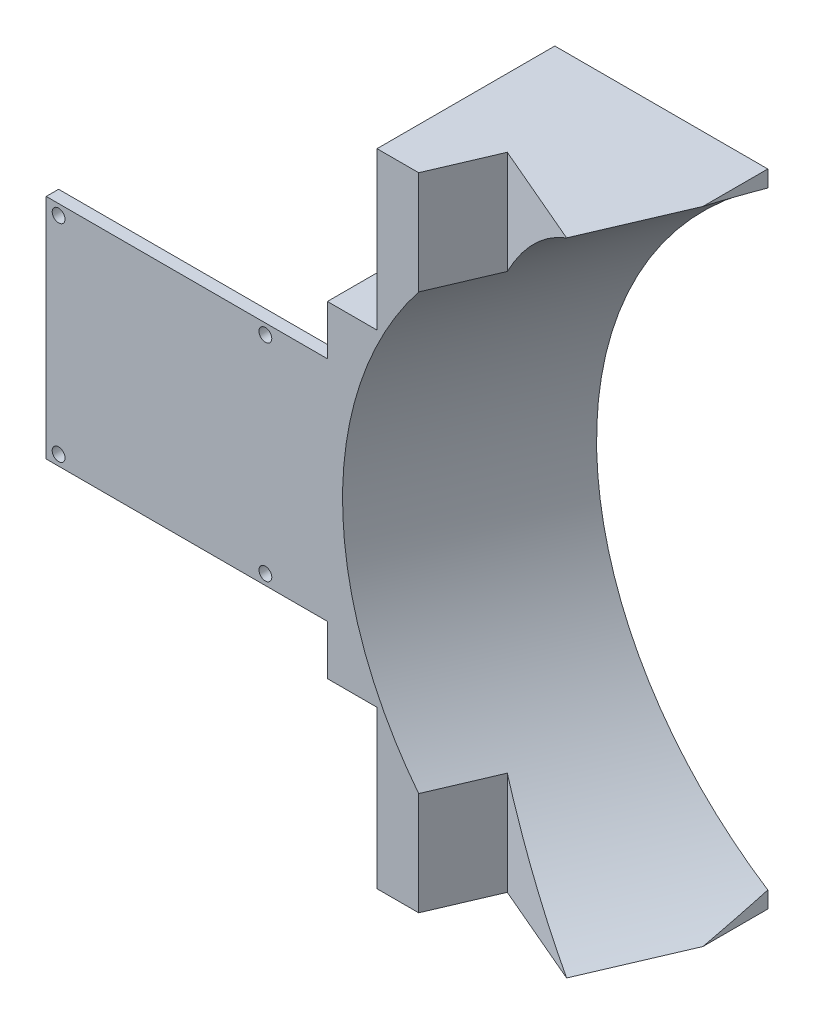
SolidWorks part; units mm, degrees
material "PTFE(普通)"
ref_plane "前视基准面" through (0, 0, 0) normal (0, 0, 1) x (1, 0, 0)
ref_plane "上视基准面" through (0, 0, 0) normal (0, 1, 0) x (1, 0, 0)
ref_plane "右视基准面" through (0, 0, 0) normal (1, 0, 0) x (0, 0, -1)
other "Configuration Table"
sketch "草图1" plane through (0, 0, 0) normal (0, 0, 1) x (1, 0, 0)
  line L1 (40, -27.5) -> (-40, -27.5)
  line L2 (40, -27.5) -> (40, 27.5)
  line L3 (40, 27.5) -> (-40, 27.5)
  line L4 (-40, -27.5) -> (-40, 27.5)
  line L5 (40, -27.5) -> (-40, 27.5) construction
  line L6 (40, 27.5) -> (-40, -27.5) construction
  point P0 (0, 0)
  dimension "D1" = 40
  dimension "D2" = 27.5
extrude "凸台-拉伸1" add sketch "草图1" along normal blind 3
sketch "草图2" plane through (0, 0, 0) normal (0, 0, -1) x (-1, 0, 0)
  line L0 (-40, 27.5) -> (40, 27.5) construction
  line L1 (40, -27.5) -> (-40, -27.5) construction
  line L2 (40, 27.5) -> (40, -27.5) construction
  line L3 (37, 25) -> (37, -25) construction
  circle A0 centre (37, 25) radius 1.55
  circle A1 centre (37, -25) radius 1.55
  circle A2 centre (-13, 25) radius 1.55
  circle A3 centre (-13, -25) radius 1.55
  dimension "D1" = 3.1
  dimension "D2" = 3.1
  dimension "D3" = 3.1
  dimension "D4" = 3.1
  dimension "D5" = 2.5
  dimension "D6" = 2.5
  dimension "D7" = 3
  dimension "D8" = 50
extrude "切除-拉伸1" cut sketch "草图2" against normal blind 24.5 contours A3 | A1 | A0 | A2
sketch "草图3" plane through (40, 0, 0) normal (1, 0, 0) x (0, 0, -1)
  line L1 (-3, 27.5) -> (0, 27.5)
  line L2 (-3, 27.5) -> (-3, -27.5)
  line L3 (-3, -27.5) -> (0, -27.5)
  line L4 (0, 27.5) -> (0, -27.5)
extrude "凸台-拉伸2" add sketch "草图3" along normal blind 1.5 separate body
sketch "草图4" plane through (0, 0, 3) normal (0, 0, 1) x (1, 0, 0)
  line L0 (40, 0) -> (41.5, 0) construction
  line L1 (40, -27.5) -> (40, 27.5) construction
  line L2 (41.5, 27.5) -> (41.5, -27.5) construction
  point P6 (0, 0)
sketch "草图5" plane through (41.5, 0, 0) normal (1, 0, 0) x (0, 0, -1)
  line L1 (-3, 27.5) -> (0, 27.5)
  line L2 (-3, 27.5) -> (-3, -27.5)
  line L3 (-3, -27.5) -> (0, -27.5)
  line L4 (0, 27.5) -> (0, -27.5)
extrude "凸台-拉伸3" add sketch "草图5" along normal blind 50
sketch "草图6" plane through (0, 27.5, 0) normal (0, 1, 0) x (1, 0, 0)
  line L1 (40, 0) -> (91.5, 0)
  line L2 (40, 0) -> (40, -3)
  line L3 (40, -3) -> (91.5, -3)
  line L4 (91.5, 0) -> (91.5, -3)
extrude "凸台-拉伸4" add sketch "草图6" along normal blind 50
sketch "草图7" plane through (0, -27.5, 0) normal (0, -1, 0) x (1, 0, 0)
  line L0 (40, 3) -> (41.5, 3) construction
  line L1 (40, 3) -> (91.5, 3)
  line L2 (40, 3) -> (40, 0)
  line L3 (40, 0) -> (91.5, 0)
  line L4 (91.5, 3) -> (91.5, 0)
  line L5 (-40, 3) -> (91.5, 3) construction
extrude "凸台-拉伸5" add sketch "草图7" along normal blind 50
sketch "草图8" plane through (0, 0, 0) normal (0, 0, -1) x (-1, 0, 0)
  line L1 (-91.5, 77.5) -> (-40, 77.5)
  line L2 (-91.5, 77.5) -> (-91.5, -77.5)
  line L3 (-91.5, -77.5) -> (-40, -77.5)
  line L4 (-40, 77.5) -> (-40, -77.5)
extrude "凸台-拉伸6" add sketch "草图8" along normal blind 40
sketch "草图9" plane through (40, 0, 0) normal (-1, 0, 0) x (0, 0, 1)
  line L0 (-40, 39.5) -> (3, 39.5)
  line L1 (-40, -77.5) -> (-40, 77.5) construction
  line L2 (3, 77.5) -> (3, 27.5) construction
  line L3 (-40, -39.5) -> (3, -39.5)
  line L4 (3, -77.5) -> (3, -27.5) construction
  line L5 (-40, 77.5) -> (3, 77.5) construction
  line L6 (3, -77.5) -> (-40, -77.5) construction
  line L7 (-40, 39.5) -> (-40, -39.5)
  line L8 (3, 39.5) -> (3, 27.5)
  line L9 (3, 27.5) -> (0, 27.5)
  line L10 (0, 27.5) -> (0, -27.5)
  line L11 (0, -27.5) -> (3, -27.5)
  line L12 (3, -27.5) -> (3, -39.5)
  dimension "D1" = 38
  dimension "D2" = 38
extrude "凸台-拉伸7" add sketch "草图9" along normal blind 12
sketch "草图10" plane through (0, 77.5, 0) normal (0, 1, 0) x (1, 0, 0)
  line L0 (40, -3) -> (91.5, -3) construction
  line L2 (91.5, -3) -> (91.5, 40) construction
  line L3 (56.5, 12) -> (91.5, -3)
  line L4 (56.5, 12) -> (50.0714, -3)
  line L5 (50.0714, -3) -> (91.5, -3)
  point P0 (56.5, 12)
  dimension "D1" = 15
  dimension "D2" = 35
sketch "草图11" plane through (0, -77.5, 0) normal (0, -1, 0) x (1, 0, 0)
  line L0 (91.5, 3) -> (56.5, -12)
extrude "切除-拉伸2" cut sketch "草图10" against normal blind 184 contours L4 L5 L3
sketch "草图13" plane through (13.1121, 0, -30.5948) normal (-0.3939, 0, 0.9191) x (0.9191, 0, 0.3939)
  line L0 (85.2835, 77.5) -> (85.2835, -77.5) construction
  line L1 (85.2835, -77.5) -> (47.2047, -77.5) construction
  circle A0 centre (120.2835, 0) radius 90
  dimension "D1" = 35
  dimension "D2" = 180
  dimension "D3" = 77.5
extrude "切除-拉伸3" cut sketch "草图13" along normal mid plane 184
